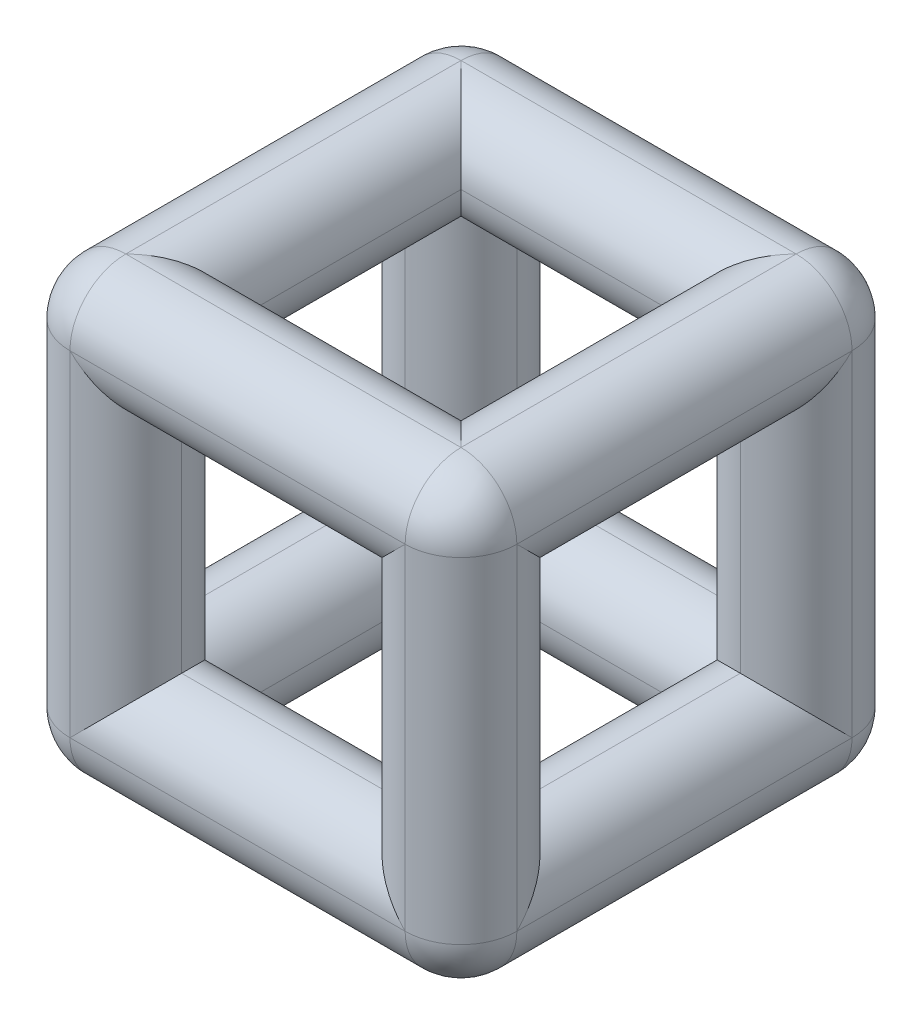
SolidWorks part; units mm, degrees
ref_plane "Front Plane" through (0, 0, 0) normal (0, 0, 1) x (1, 0, 0)
ref_plane "Top Plane" through (0, 0, 0) normal (0, 1, 0) x (1, 0, 0)
ref_plane "Right Plane" through (0, 0, 0) normal (1, 0, 0) x (0, 0, -1)
sketch "Sketch4" plane through (0, 0, 0) normal (1, 0, 0) x (0, 0, -1)
  line L1 (0, 0) -> (20, 0)
  line L2 (0, 0) -> (0, 20)
  line L3 (0, 20) -> (20, 20)
  line L4 (20, 0) -> (20, 20)
  dimension "D1" = 20
extrude "Boss-Extrude1" add sketch "Sketch4" along normal blind 20
sketch "Sketch5" plane through (0, 0, 0) normal (0, 0, 1) x (1, 0, 0)
  line L0 (0, 0) -> (20, 20) construction
  line L1 (5, 5) -> (15, 5)
  line L2 (5, 5) -> (5, 15)
  line L3 (5, 15) -> (15, 15)
  line L4 (15, 5) -> (15, 15)
  line L5 (20, 0) -> (0, 0) construction
  dimension "D1" = 10
  dimension "D2" = 5
extrude "Cut-Extrude1" cut sketch "Sketch5" against normal through all
sketch "Sketch6" plane through (0, 20, 0) normal (0, 1, 0) x (1, 0, 0)
  line L0 (0, 0) -> (20, 20) construction
  line L1 (0, 20) -> (0, 0) construction
  line L2 (5, 5) -> (15, 5)
  line L3 (5, 5) -> (5, 15)
  line L4 (5, 15) -> (15, 15)
  line L5 (15, 5) -> (15, 15)
  dimension "D1" = 10
  dimension "D2" = 5
extrude "Cut-Extrude2" cut sketch "Sketch6" against normal through all
sketch "Sketch7" plane through (20, 0, 0) normal (1, 0, 0) x (0, 0, -1)
  line L0 (0, 0) -> (20, 20) construction
  line L1 (0, 20) -> (0, 0) construction
  line L2 (5, 5) -> (15, 5)
  line L3 (5, 5) -> (5, 15)
  line L4 (5, 15) -> (15, 15)
  line L5 (15, 5) -> (15, 15)
  dimension "D1" = 10
  dimension "D2" = 5
extrude "Cut-Extrude3" cut sketch "Sketch7" against normal through all
fillet "Fillet1" radius 2.5 36 edges at (15, 10, -20) (10, 5, -20) (5, 10, -20) (10, 15, -20) (10, 0, -20) (15, 0, -10) (10, 0, -5) (5, 0, -10) (10, 0, -15) (0, 0, -10) (0, 10, -20) (0, 15, -10) (0, 10, -15) (0, 5, -10) (0, 10, -5) (10, 0, 0) (0, 10, 0) (15, 10, 0) (10, 15, 0) (5, 10, 0) (10, 5, 0) (10, 20, -20) (10, 20, 0) (0, 20, -10) (15, 20, -10) (10, 20, -15) (5, 20, -10) (10, 20, -5) (20, 20, -10) (20, 10, -20) (20, 0, -10) (20, 10, 0) (20, 10, -15) (20, 15, -10) (20, 10, -5) (20, 5, -10)
fillet "Fillet3" radius 2.5 4 edges at (10, 5, -5) (10, 5, -15) (5, 15, -10) (15, 15, -10)
fillet "Fillet4" radius 2.5 4 edges at (15, 10, -15) (5, 10, -15) (5, 10, -5) (15, 10, -5)
fillet "Fillet5" radius 2.5 4 edges at (10, 15, -15) (10, 15, -5) (15, 5, -10) (5, 5, -10)
